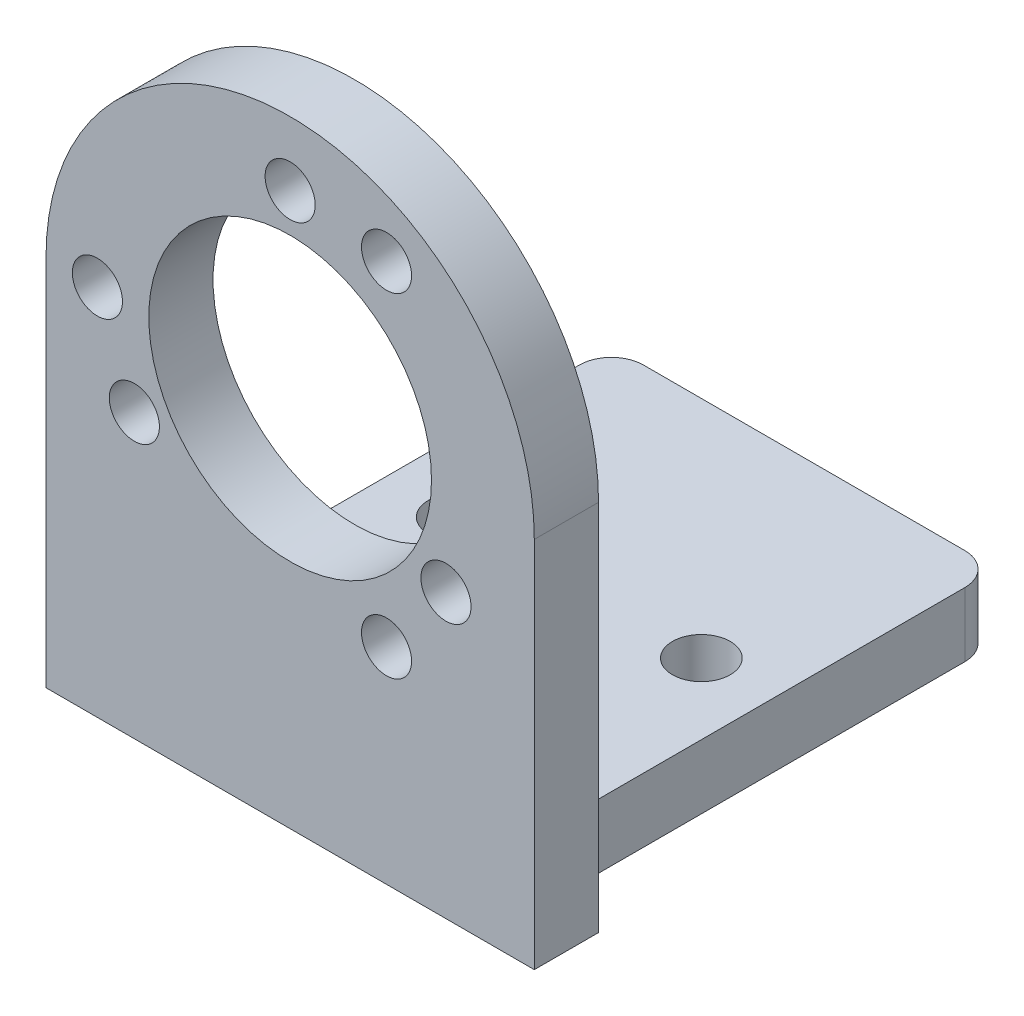
SolidWorks part; units mm, degrees
material "ABS"
ref_plane "Front Plane" through (0, 0, 0) normal (0, 0, 1) x (1, 0, 0)
ref_plane "Top Plane" through (0, 0, 0) normal (0, 1, 0) x (1, 0, 0)
ref_plane "Right Plane" through (0, 0, 0) normal (1, 0, 0) x (0, 0, -1)
sketch "Sketch1" plane through (0, 0, 0) normal (0, 0, 1) x (1, 0, 0)
  line L0 (-19, 0) -> (-19, -29)
  line L1 (-19, -29) -> (19, -29)
  line L2 (19, -29) -> (19, 0)
  circle A0 centre (0, 0) radius 19
  circle A1 centre (0, 0) radius 11
  dimension "D1" = 38
  dimension "D2" = 10
  dimension "D3" = 22
extrude "Boss-Extrude1" add sketch "Sketch1" along normal blind 5 contours A0 A1 | A0 L0 L1 L2 region at (0, -21.3225, 0) region at (0, 18.4626, 0)
sketch "Sketch2" plane through (0, 0, 0) normal (0, 0, -1) x (-1, 0, 0)
  line L1 (-15, -29) -> (15, -29)
  line L2 (-15, -29) -> (-15, -24)
  line L3 (-15, -24) -> (15, -24)
  line L4 (15, -29) -> (15, -24)
  line L5 (19, -29) -> (-19, -29) construction
  point P8 (0, -24)
  dimension "D1" = 5
  dimension "D2" = 30
extrude "Boss-Extrude2" add sketch "Sketch2" along normal blind 35
hole_wizard "M3 Clearance Hole1" positions "Sketch3" profile "Sketch4" hole size "M3" standard "ANSI Metric" end condition up to next
sketch "Sketch3" plane through (0, 0, 5) normal (0, 0, 1) x (1, 0, 0)
  line L0 (0, 0) -> (0, 14) construction
  line L2 (0, 0) -> (7.5, 12.9904) construction
  circle A0 centre (0, 0) radius 14 construction
  circle A1 centre (0, 0) radius 15 construction
  point P5 (0, 14)
  point P14 (12.1244, -7)
  point P15 (-12.1244, -7)
  point P19 (7.5, 12.9904)
  point P32 (7.5, -12.9904)
  point P33 (-15, 0)
  dimension "D1" = 28
  dimension "D2" = 3
  dimension "D3" = 30
  dimension "D4" = 30
sketch "Sketch4" plane through (-15, 0, 5) normal (1, 0, 0) x (0, -1, 0)
  line L0 (0, 0) -> (0, 5)
  line L1 (0, 5) -> (1.95, 5)
  line L2 (1.95, 5) -> (1.95, 0)
  line L5 (1.95, 0) -> (0, 0)
  line L11 (0, -6.35) -> (0, 107.95) construction
  dimension "Thru Hole Dia." = 3.9
  dimension "Thru Hole Depth" = 5
hole_wizard "M4 Clearance Hole1" positions "Sketch5" profile "Sketch6" hole size "M4" standard "ANSI Metric" end condition up to next
sketch "Sketch5" plane through (0, -24, 0) normal (0, 1, 0) x (1, 0, 0)
  line L0 (9.5, 17.5) -> (-9.5, 17.5) construction
  line L1 (-15, 35) -> (15, 35) construction
  point P1 (-9.5, 17.5)
  point P20 (9.5, 17.5)
  point P24 (0, 17.5)
  dimension "D1" = 19
  dimension "D2" = 17.5
sketch "Sketch6" plane through (-9.5, -24, -17.5) normal (1, 0, 0) x (0, 0, 1)
  line L0 (0, 0) -> (0, 5)
  line L1 (0, 5) -> (2.25, 5)
  line L2 (2.25, 5) -> (2.25, 0)
  line L5 (2.25, 0) -> (0, 0)
  line L11 (0, -6.35) -> (0, 107.95) construction
  dimension "Thru Hole Dia." = 4.5
  dimension "Thru Hole Depth" = 5
fillet "Fillet1" radius 2.5 5 edges at (-15, -26.5, -35) (15, -26.5, -35) (0, -24, 0) (-15, -26.5, 0) (15, -26.5, 0)
